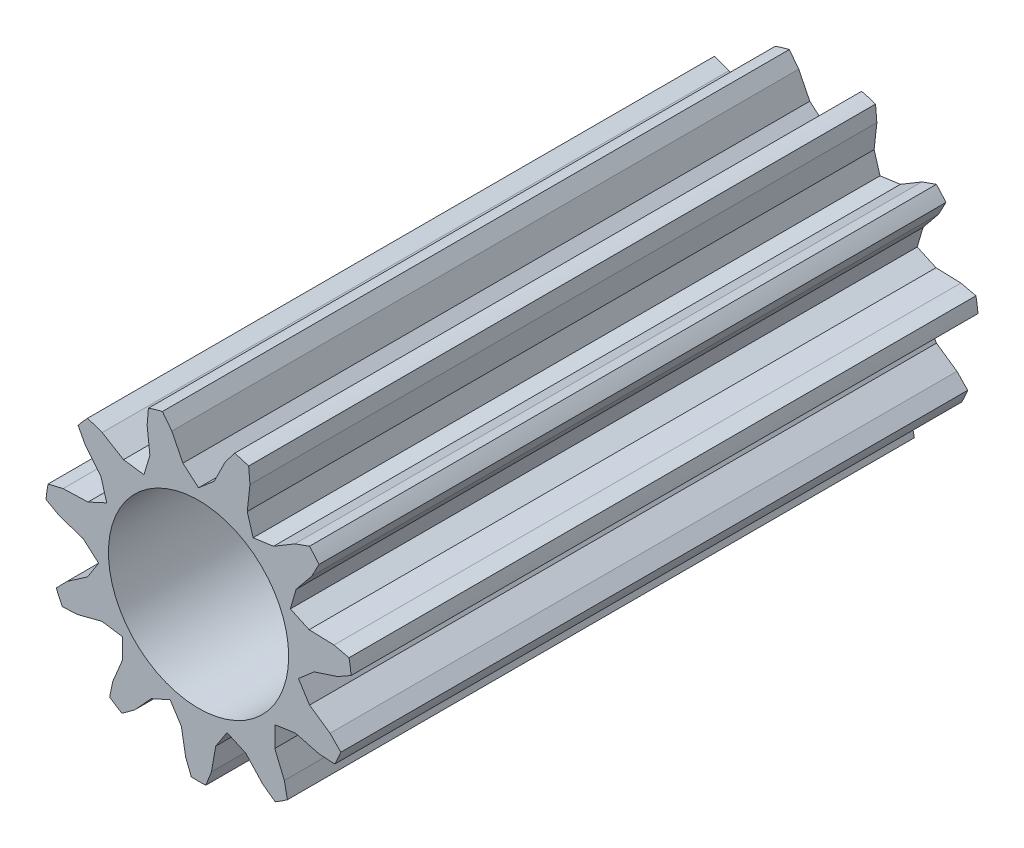
SolidWorks part; units mm, degrees
ref_plane "Front Plane" through (0, 0, 0) normal (0, 0, 1) x (1, 0, 0)
ref_plane "Top Plane" through (0, 0, 0) normal (0, 1, 0) x (1, 0, 0)
ref_plane "Right Plane" through (0, 0, 0) normal (1, 0, 0) x (0, 0, -1)
sketch "Sketch1" plane through (0, 0, 0) normal (0, 0, 1) x (1, 0, 0)
  line L1 (4.0659, -4.0659) -> (-4.0659, -4.0659) construction
  line L2 (4.0659, -4.0659) -> (4.0659, 4.0659) construction
  line L3 (4.0659, 4.0659) -> (-4.0659, 4.0659) construction
  line L4 (-4.0659, -4.0659) -> (-4.0659, 4.0659) construction
  line L5 (4.0659, -4.0659) -> (-4.0659, 4.0659) construction
  line L6 (4.0659, 4.0659) -> (-4.0659, -4.0659) construction
  circle A0 centre (0, 0) radius 9.7778
  circle A1 centre (0, 0) radius 5.75 construction
  dimension "D1" = 19.5556
  dimension "D2" = 11.5
extrude "Boss-Extrude1" add sketch "Sketch1" along normal blind 40
sketch "Sketch2" plane through (0, 0, 0) normal (0, 0, 1) x (1, 0, 0)
  line L0 (0, 0) -> (0, 10.088) construction
  line L1 (0, 6.4402) -> (-0.9985, 7.2997)
  line L8 (-1.7043, 10.285) -> (0, 10.9993)
  line L11 (-0.9985, 7.2997) -> (-1.7043, 8.7207)
  line L12 (-1.7043, 8.7207) -> (-2.3066, 9.5018)
  line L13 (-2.3066, 9.5018) -> (-1.7043, 10.285)
  line L14 (2.3066, 9.5018) -> (1.7043, 10.285)
  line L15 (1.7043, 8.7207) -> (2.3066, 9.5018)
  line L16 (0.9985, 7.2997) -> (1.7043, 8.7207)
  line L17 (1.7043, 10.285) -> (0, 10.9993)
  line L18 (0, 6.4402) -> (0.9985, 7.2997)
  circle A14 centre (0, 0) radius 9.7778 construction
  point P16 (0, 9.7778)
  dimension "D5" = 0.6023
  dimension "D6" = 0.7811
  dimension "D1" = 0.9985
  dimension "D2" = 0.8594
  dimension "D3" = 0.7058
  dimension "D4" = 1.4211
  dimension "D7" = 0.7832
  dimension "D8" = 0.6023
  dimension "D9" = 0.7142
  dimension "D10" = 1.7043
extrude "Cut-Extrude1" cut sketch "Sketch2" along normal through all
sketch "Sketch3" plane through (0, 0, 0) normal (0, 0, 1) x (1, 0, 0)
  circle A0 centre (0, 0) radius 7.5
  dimension "D1" = 15
sketch "Sketch4" plane through (0, 0, 40) normal (0, 0, 1) x (1, 0, 0)
  circle A0 centre (0, 0) radius 5.75
  dimension "D1" = 11.5
extrude "Cut-Extrude2" cut sketch "Sketch4" against normal through all both and the other way through all
pattern_circular "CirPattern1" count 11 over 360 about axis through (0, 0, 40) along (0, 0, -1) of "Cut-Extrude1" reverse direction yes
sketch "Sketch5" plane through (0, 0, 0) normal (0, 0, 1) x (1, 0, 0)
  line L0 (0, 0) -> (0, 16.5734) construction
  arc A0 (0, 2.7703) -> (-2.7395, 5.5802) centre (3.9333, 9.3453) cw
  arc A1 (-2.7395, 5.5802) -> (0, 7.0858) centre (3.4783, -2.4876) cw
  arc A2 (2.7395, 5.5802) -> (0, 7.0858) centre (-3.4783, -2.4876) ccw
  arc A3 (0, 2.7703) -> (2.7395, 5.5802) centre (-3.9333, 9.3453) ccw
equation "\"circle\"=19.5556"
equation "\"D1@Sketch1\"=\"circle\""
equation "\"separator_width\"=45"
equation "\"big-gear-thiccness\"=2"
equation "\"D1@Boss-Extrude1\"=\"separator_width\" - \"big-gear-thiccness\"-10/2+2"
